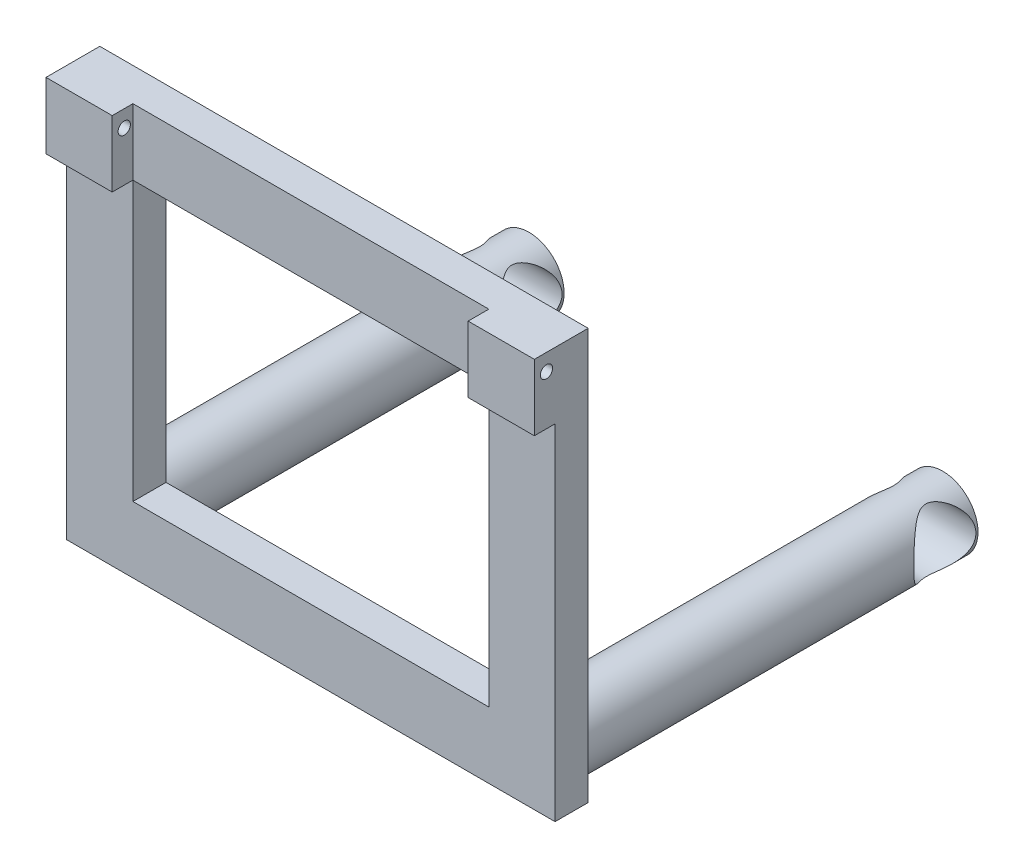
SolidWorks part; units mm, degrees
ref_plane "Front Plane" through (0, 0, 0) normal (0, 0, 1) x (1, 0, 0)
ref_plane "Top Plane" through (0, 0, 0) normal (0, 1, 0) x (1, 0, 0)
ref_plane "Right Plane" through (0, 0, 0) normal (1, 0, 0) x (0, 0, -1)
sketch "Sketch1" plane through (0, 0, 0) normal (0, 0, 1) x (1, 0, 0)
  line L0 (-796.3832, -7.0403) -> (-796.3832, -679.6151)
  line L1 (-956.3832, 152.9597) -> (223.6879, 152.9597)
  line L2 (-956.3832, 152.9597) -> (-956.3832, -839.6151)
  line L3 (-956.3832, -839.6151) -> (223.6879, -839.6151)
  line L4 (223.6879, 152.9597) -> (223.6879, -839.6151)
  line L9 (-796.3832, -679.6151) -> (63.6879, -679.6151)
  line L10 (63.6879, -7.0403) -> (63.6879, -679.6151)
  line L11 (-796.3832, -7.0403) -> (63.6879, -7.0403)
  point P8 (-603.3444, -570.2499)
  point P9 (-653.3655, -665.5411)
  point P10 (-956.3832, -839.6151)
  dimension "D1" = 160
extrude "Boss-Extrude2" add sketch "Sketch1" along normal blind 80
sketch "Sketch2" plane through (0, 0, 80) normal (0, 0, 1) x (1, 0, 0)
  line L1 (-956.3832, 152.9597) -> (-796.3832, 152.9597)
  line L2 (-956.3832, 152.9597) -> (-956.3832, -7.0403)
  line L3 (-956.3832, -7.0403) -> (-796.3832, -7.0403)
  line L4 (-796.3832, 152.9597) -> (-796.3832, -7.0403)
  line L5 (63.6879, -7.0403) -> (223.6879, -7.0403)
  line L6 (63.6879, -7.0403) -> (63.6879, 152.9597)
  line L7 (63.6879, 152.9597) -> (223.6879, 152.9597)
  line L8 (223.6879, -7.0403) -> (223.6879, 152.9597)
extrude "Boss-Extrude3" add sketch "Sketch2" along normal blind 50
sketch "Sketch3" plane through (223.6879, 0, 0) normal (1, 0, 0) x (0, 0, -1)
  circle A0 centre (-100.8438, 112.4049) radius 14.8547
  point P2 (-100.8438, 112.4049)
extrude "Cut-Extrude1" cut sketch "Sketch3" against normal through all and the other way through all
sketch "Sketch4" plane through (0, 0, 0) normal (0, 0, -1) x (-1, 0, 0)
  line L0 (956.3832, 152.9597) -> (956.3832, -839.6151) construction
  line L1 (-223.6879, -839.6151) -> (-223.6879, 152.9597) construction
  line L2 (956.3832, -839.6151) -> (-223.6879, -839.6151) construction
  circle A1 centre (-133.6879, -749.6151) radius 85
  circle A2 centre (866.3832, -749.6151) radius 85
  point P9 (862.8945, -749.6151)
  dimension "D1" = 170
  dimension "D4" = 170
  dimension "D5" = 90
  dimension "D2" = 90
  dimension "D3" = 90
  dimension "D6" = 90
extrude "Boss-Extrude4" add sketch "Sketch4" along normal blind 947
ref_plane "Plane1" through (233.6879, 0, 0) normal (1, 0, 0) x (0, 0, -1)
sketch "Sketch5" plane through (233.6879, 0, 0) normal (1, 0, 0) x (0, 0, -1)
  line L0 (947, -834.6151) -> (947, -664.6151) construction
  circle A0 centre (867, -748.9105) radius 75
  dimension "D1" = 150
  dimension "D2" = 80
extrude "Cut-Extrude2" cut sketch "Sketch5" against normal through all
